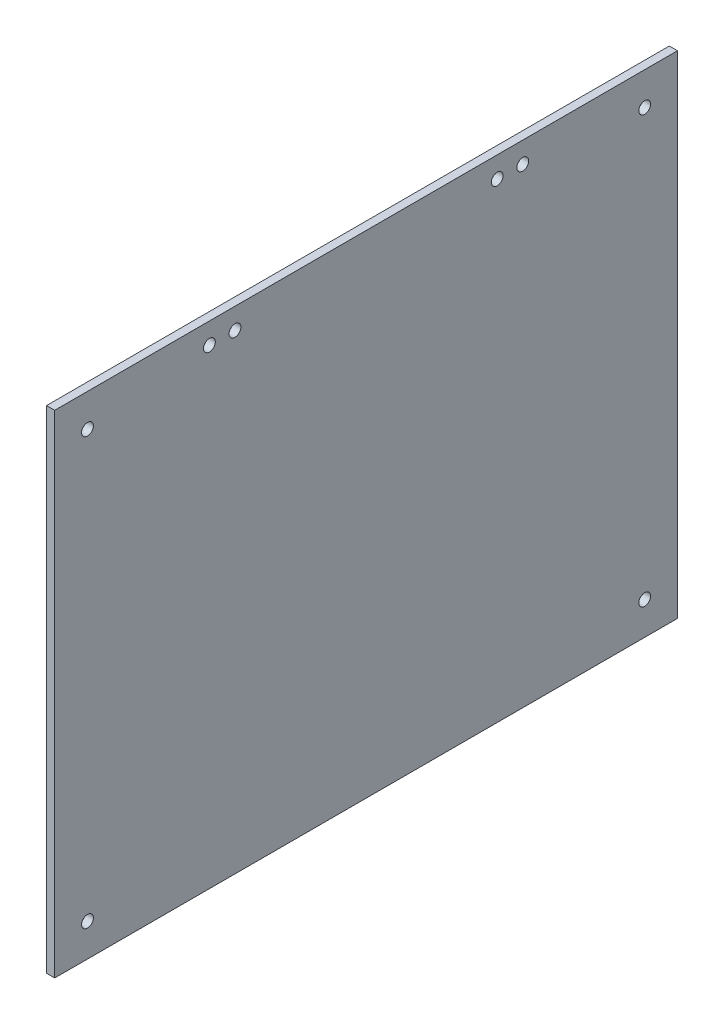
SolidWorks part; units mm, degrees
ref_plane "Front Plane" through (0, 0, 0) normal (0, 0, 1) x (1, 0, 0)
ref_plane "Top Plane" through (0, 0, 0) normal (0, 1, 0) x (1, 0, 0)
ref_plane "Right Plane" through (0, 0, 0) normal (1, 0, 0) x (0, 0, -1)
sketch "Sketch1" plane through (0, 0, 0) normal (1, 0, 0) x (0, 0, -1)
  line L1 (0, 0) -> (241.3, 0)
  line L2 (0, 0) -> (0, 190.5)
  line L3 (0, 190.5) -> (241.3, 190.5)
  line L4 (241.3, 0) -> (241.3, 190.5)
  dimension "D1" = 241.3
  dimension "D2" = 190.5
extrude "Boss-Extrude1" add sketch "Sketch1" along normal blind 3.175
sketch "Sketch2" plane through (3.175, 0, 0) normal (1, 0, 0) x (0, 0, -1)
  line L2 (-1000, 95.25) -> (49000, 95.25) construction
  line L3 (0, 190.5) -> (0, 0) construction
  line L4 (120.65, -809.5) -> (120.65, 49190.5) construction
  line L5 (241.3, 190.5) -> (0, 190.5) construction
  line L6 (1228.6, 95.25) -> (-48771.4, 95.25) construction
  line L7 (0, 0) -> (241.3, 0) construction
  line L8 (241.3, 0) -> (241.3, 190.5) construction
  circle A8 centre (228.6, 12.7) radius 2.286
  circle A9 centre (228.6, 177.8) radius 2.286
  circle A10 centre (12.7, 12.7) radius 2.286
  circle A11 centre (12.7, 177.8) radius 2.286
  point P15 (0, 95.25)
  point P20 (120.65, 190.5)
  dimension "D1" = 4.572
  dimension "D2" = 12.7
  dimension "D3" = 12.7
extrude "Cut-Extrude1" cut sketch "Sketch2" against normal through all
sketch "Sketch3" plane through (3.175, 0, 0) normal (1, 0, 0) x (0, 0, -1)
  line L0 (62.23, 182.372) -> (67.564, 182.372) construction
  line L1 (173.736, 182.372) -> (179.07, 182.372) construction
  line L2 (241.3, 190.5) -> (0, 190.5) construction
  circle A0 centre (59.944, 182.372) radius 2.286
  circle A1 centre (69.85, 182.372) radius 2.286
  circle A2 centre (171.45, 182.372) radius 2.286
  circle A3 centre (181.356, 182.372) radius 2.286
  point P14 (120.65, 190.5)
  dimension "D2" = 4.572
  dimension "D1" = 5.334
  dimension "D3" = 5.334
  dimension "D4" = 8.128
  dimension "D5" = 50.8
  dimension "D6" = 50.8
extrude "Cut-Extrude2" cut sketch "Sketch3" against normal through all
